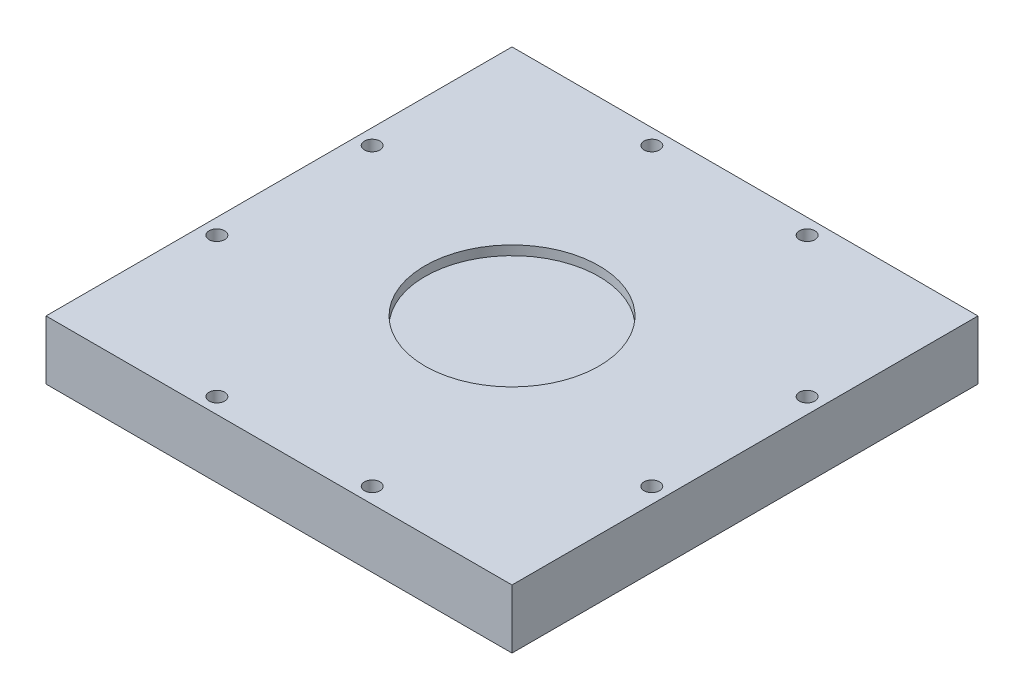
SolidWorks part; units mm, degrees
ref_plane "Front Plane" through (0, 0, 0) normal (0, 0, 1) x (1, 0, 0)
ref_plane "Top Plane" through (0, 0, 0) normal (0, 1, 0) x (1, 0, 0)
ref_plane "Right Plane" through (0, 0, 0) normal (1, 0, 0) x (0, 0, -1)
sketch "Sketch1" plane through (0, 0, 0) normal (0, 1, 0) x (1, 0, 0)
  line L1 (0, 0) -> (150, 0)
  line L2 (0, 0) -> (0, 150)
  line L3 (0, 150) -> (150, 150)
  line L4 (150, 0) -> (150, 150)
  dimension "D1" = 150
  dimension "D2" = 150
extrude "Boss-Extrude1" add sketch "Sketch1" along normal blind 19
sketch "Sketch2" plane through (0, 19, 0) normal (0, 1, 0) x (1, 0, 0)
  line L0 (75, 150) -> (75, 0) construction
  line L1 (150, 150) -> (0, 150) construction
  line L2 (0, 0) -> (150, 0) construction
  circle A0 centre (75, 75) radius 28
  dimension "D1" = 56
extrude "Cut-Extrude1" cut sketch "Sketch2" against normal blind 3
sketch "Sketch3" plane through (0, 19, 0) normal (0, 1, 0) x (1, 0, 0)
  line L1 (150, 0) -> (150, 150) construction
  line L2 (0, 0) -> (150, 0) construction
  line L3 (0, 150) -> (0, 0) construction
  circle A1 centre (100, 5) radius 2.5
  circle A2 centre (50, 5) radius 2.5
  dimension "D1" = 5
  dimension "D3" = 5
  dimension "D5" = 5
  dimension "D2" = 50
  dimension "D4" = 50
ref_point "Point1"
ref_axis "Axis1" through (75, 16, -75) along (0, 1, 0)
extrude "Cut-Extrude2" cut sketch "Sketch3" against normal blind 5
pattern_circular "CirPattern1" count 4 over 360 about axis through (75, 16, -75) along (0, 1, 0) of "Cut-Extrude2"
